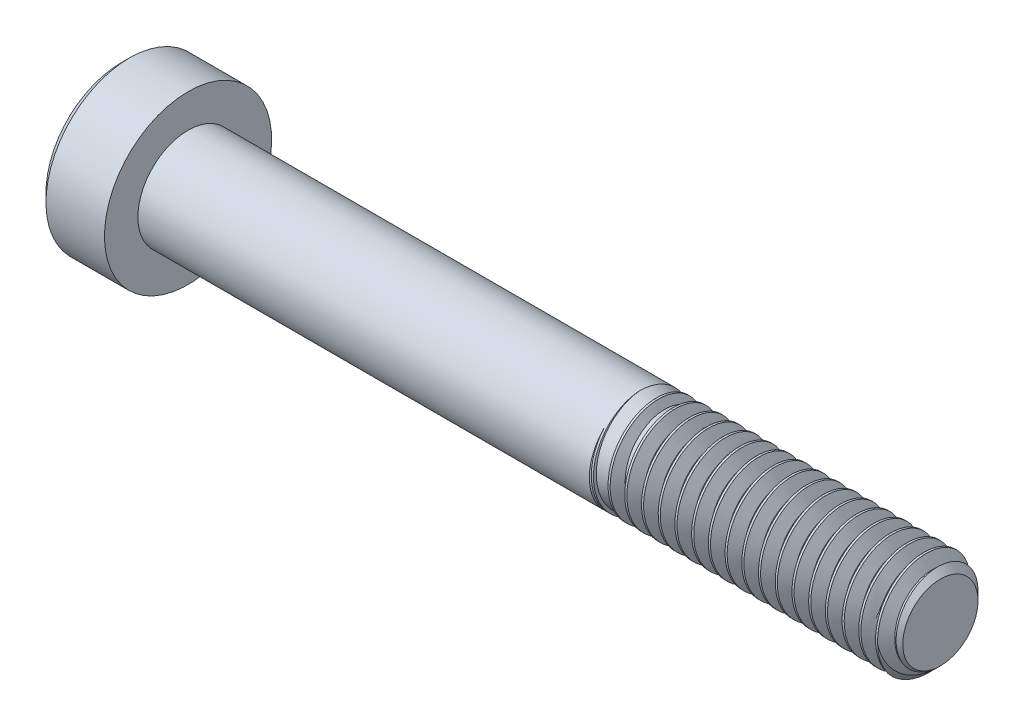
SolidWorks part; units mm, degrees
ref_plane "Front Plane" through (0, 0, 0) normal (0, 0, 1) x (1, 0, 0)
ref_plane "Top Plane" through (0, 0, 0) normal (0, 1, 0) x (1, 0, 0)
ref_plane "Right Plane" through (0, 0, 0) normal (1, 0, 0) x (0, 0, -1)
sketch "Sketch1" plane through (0, 0, 0) normal (0, 0, 1) x (1, 0, 0)
  line L0 (22.5, 0) -> (-22.5, 0) construction
  line L1 (22.5, 3) -> (22.5, -3) construction
  line L2 (-22.5, 5) -> (-22.5, -5) construction
  line L3 (-22.5, 5) -> (-26, 5) construction
  line L4 (-26, 5) -> (-26.5, 4.5) construction
  line L5 (-26.5, 4.5) -> (-26.5, -4.5) construction
  line L6 (-26.5, -4.5) -> (-26, -5) construction
  line L7 (-26, -5) -> (-22.5, -5) construction
  line L8 (4.5, 3) -> (4.5, -3) construction
  line L9 (22.4375, 3.1083) -> (23.4375, 3.1083) construction
  line L10 (23.4375, 3.1083) -> (22.9375, 2.2422) construction
  line L11 (22.9375, 2.2422) -> (22.4375, 3.1083) construction
  line L12 (22.9375, 3.1083) -> (22.9375, 3) construction
  line L13 (22.9375, 2.2422) -> (22.9375, 2.3505) construction
  line L14 (22.5, 3) -> (23.375, 3) construction
  line L15 (22.875, 2.3505) -> (23, 2.3505)
  line L16 (22.4688, 3.0541) -> (23.4062, 3.0541)
  line L17 (23.4062, 3.0541) -> (23, 2.3505)
  line L18 (22.875, 2.3505) -> (22.4688, 3.0541)
  line L19 (-23.38, -2) -> (-23.38, 2)
  point P7 (-23.38, 0)
  point P12 (19, -3)
  point P24 (22.9375, 3)
  point P27 (22.9375, 2.3505)
  point P30 (22.9375, 3.0541)
  point P34 (-23.38, 0)
  dimension "D1" = 45
  dimension "Thread Size" = 6
  dimension "Length" = 45
  dimension "Head DiameterSketch1" = 10
  dimension "Head Height" = 4
  dimension "Hex Depth" = 3.12
  dimension "Chamfer" = 0.5
  dimension "D2" = 3.5
  dimension "Thread Pitch" = 1
  dimension "D3" = 0.125
  dimension "Drive Size" = 4
ref_plane "Plane1" through (22.5, 0, 0) normal (1, 0, 0) x (0, 0, -1)
ref_plane "Plane2" through (-26.5, 0, 0) normal (1, 0, 0) x (0, 0, -1)
sketch "Sketch2" plane through (22.5, 0, 0) normal (1, 0, 0) x (0, 0, -1)
  circle A0 centre (0, 0) radius 3
extrude "Boss-Extrude1" add sketch "Sketch2" against normal up to vertex (18 mm away) up to point (4.5, 3, 0)
sketch "Sketch3" plane through (22.5, 0, 0) normal (1, 0, 0) x (0, 0, -1)
  circle A0 centre (0, 0) radius 3 construction
  circle A1 centre (0, 0) radius 3
chamfer "Chamfer1" distance 0.75 angle 45 1 edges at (22.5, 0, -3)
sketch "Sketch4" plane through (-26.5, 0, 0) normal (1, 0, 0) x (0, 0, -1)
  line L0 (-5, 0.7937) -> (5, 0.7937) construction
  line L1 (0, 2.3094) -> (-2, 1.1547)
  line L2 (-2, 1.1547) -> (-2, -1.1547)
  line L3 (-2, -1.1547) -> (0, -2.3094)
  line L4 (0, -2.3094) -> (2, -1.1547)
  line L5 (2, -1.1547) -> (2, 1.1547)
  line L6 (2, 1.1547) -> (0, 2.3094)
  line L7 (0, 0) -> (0, 0.7937) construction
  circle A0 centre (0, 0) radius 2 construction
  dimension "D1" = 10
  dimension "D2" = 0.7937
sketch "Sketch10" plane through (0, 0, 0) normal (0, 0, 1) x (1, 0, 0)
  line L0 (-22.5, 0) -> (6.2321, 0) construction
  line L1 (6.2321, 0) -> (4.5, 3)
  line L2 (4.5, 3) -> (-22.5, 3)
  line L3 (-22.5, 3) -> (-22.5, 0)
  line L4 (-22.5, 5) -> (-22.5, -5) construction
  line L5 (-22.5, 0) -> (6.2321, 0)
  dimension "D1" = 60
revolve "Revolve2" add sketch "Sketch10" angle 360 about L0
sketch "Sketch6" plane through (0, 0, 0) normal (0, 0, 1) x (1, 0, 0)
  line L0 (-26, 5) -> (-26.5, 4.5) construction
  line L1 (-22.5, 5) -> (-26, 5) construction
  line L2 (-22.5, 5) -> (-22.5, -5) construction
  line L3 (-26.5, 4.5) -> (-26.5, -4.5) construction
  line L4 (-26, 5) -> (-26.5, 4.5)
  line L5 (-22.5, 5) -> (-26, 5)
  line L6 (-22.5, 5) -> (-22.5, 0)
  line L7 (-26.5, 4.5) -> (-26.5, 0)
  line L8 (-22.5, 0) -> (-26.5, 0) construction
  line L9 (-22.5, 0) -> (-26.5, 0)
revolve "Revolve1" add sketch "Sketch6" angle 360 about L8
extrude "Cut-Extrude1" cut sketch "Sketch4" along normal up to vertex (3.12 mm away) up to point (-23.38, 0, 0)
sketch "Sketch8" plane through (-26.5, 0, 0) normal (-1, 0, 0) x (0, 0, 1)
  circle A1 centre (0, 0) radius 2.3094
extrude "Cut-Extrude2" cut sketch "Sketch8" against normal through all draft 45
curve "Helix/Spiral1" pitch 1 height 19 turns 19 parameters "Pitch"=1
ref_plane "Plane3" through (4.5, 3, 0) normal (-1, 0, 0) x (0, 0, 1)
split "Split1" trim tools "Plane3" bodies to split 105 resulting bodies 108 109
sketch "Sketch5" plane through (0, 0, 0) normal (0, 0, 1) x (1, 0, 0)
  line L0 (22.4688, 3.0541) -> (23.4062, 3.0541) construction
  line L1 (22.875, 2.3505) -> (22.4688, 3.0541) construction
  line L2 (22.875, 2.3505) -> (23, 2.3505) construction
  line L3 (23.4062, 3.0541) -> (23, 2.3505) construction
  line L4 (22.4688, 3.0541) -> (23.4062, 3.0541)
  line L5 (22.875, 2.3505) -> (22.4688, 3.0541)
  line L6 (22.875, 2.3505) -> (23, 2.3505)
  line L7 (23.4062, 3.0541) -> (23, 2.3505)
sweep "Cut-Sweep1" cut profiles "Sketch5" path "Helix/Spiral1" align with end faces yes
sketch "Sketch11" plane through (4.5, 3, 0) normal (-1, 0, 0) x (0, 0, 1)
  line L0 (0, 0) -> (0, -6) construction
  circle A0 centre (0, -3) radius 3
extrude "Boss-Extrude2" add sketch "Sketch11" against normal blind 10 draft 20
equation "\"D3@Helix/Spiral1\" = \"Minimum Thread Length@Sketch1\" + \"Pitch@Helix/Spiral1\""
equation "\"D1@Chamfer1\" = \"Pitch@Helix/Spiral1\"*.75"
equation "\"D2@Sketch1\"=\"Pitch@Helix/Spiral1\"*3.5"
equation "\"D1@Sketch4\" = \"Head DiameterSketch1@Sketch1\""
equation "\"Chamfer@Sketch1\" = \"Head Height@Sketch1\"/8"
equation "\"D3@Sketch1\"=\"Thread Pitch@Sketch1\"/8"
equation "\"Pitch@Helix/Spiral1\"=\"Thread Pitch@Sketch1\""
